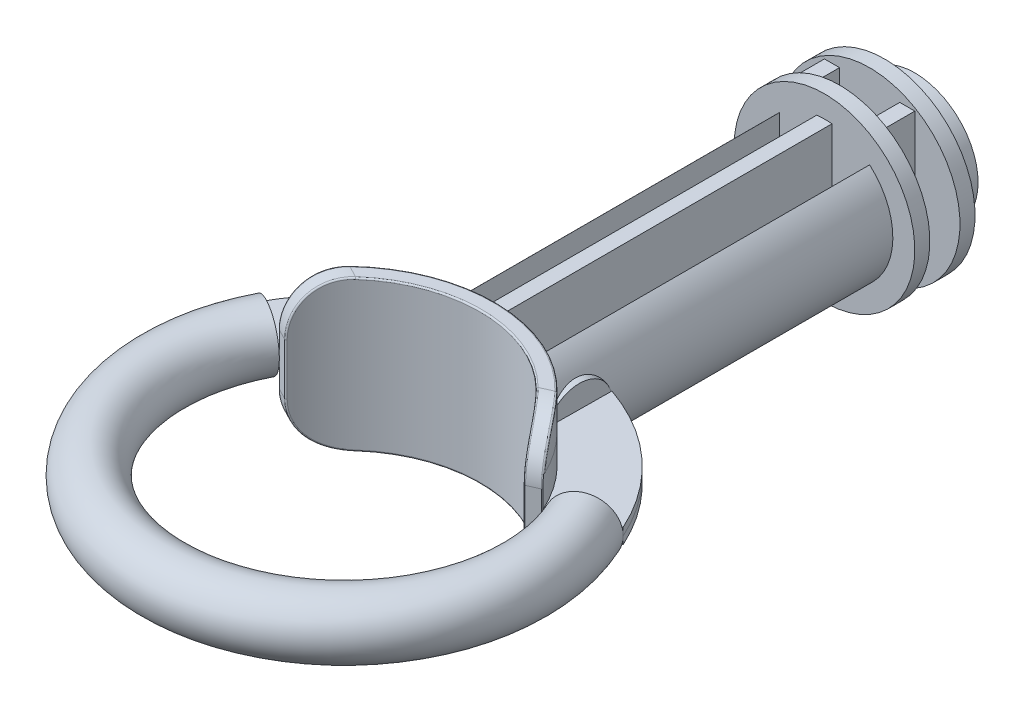
SolidWorks part; units mm, degrees
ref_plane "Front Plane" through (0, 0, 0) normal (0, 0, 1) x (1, 0, 0)
ref_plane "Top Plane" through (0, 0, 0) normal (0, 1, 0) x (1, 0, 0)
ref_plane "Right Plane" through (0, 0, 0) normal (1, 0, 0) x (0, 0, -1)
ref_axis "Axis1" through (0, 55, 0) along (0, -1, 0)
sketch "Sketch2" plane through (0, 0, 0) normal (0, 0, 1) x (1, 0, 0)
  circle A0 centre (12, 0) radius 2
  dimension "D1" = 12
revolve "Revolve1" add sketch "Sketch2" angle 360 about axis through (0, 55, 0) along (0, -1, 0)
ref_plane "Plane1" through (0, 0, -9.9) normal (0, 0, 1) x (1, 0, 0)
sketch "Sketch3" plane through (0, 0, -9.9) normal (0, 0, 1) x (1, 0, 0)
  circle A0 centre (0, 0) radius 4.5427
extrude "Boss-Extrude1" add sketch "Sketch3" against normal blind 22 and the other way blind 0.88
sketch "Sketch6" plane through (0, 0, 0) normal (0, 1, 0) x (1, 0, 0)
  line L0 (-8.901, 4.5576) -> (-8.0225, 4.1078)
  line L1 (9.1173, 4.1078) -> (8.2175, 3.7024)
  arc A0 (9.1173, 4.1078) -> (-8.901, 4.5576) centre (0, 0) ccw
  arc A1 (8.2175, 3.7024) -> (-8.0225, 4.1078) centre (0, 0) ccw
extrude "Boss-Extrude10" add sketch "Sketch6" along normal blind 5 and the other way blind 5 separate body
sketch "Sketch7" plane through (0, 0, -31.9) normal (0, 0, -1) x (-1, 0, 0)
  circle A0 centre (0, 0) radius 6
extrude "Boss-Extrude11" add sketch "Sketch7" along normal blind 1
fillet "Fillet1" radius 3.3 4 edges at (8.6674, 5, -3.9051) (-8.4617, 5, -4.3327) (-8.4617, -5, -4.3327) (8.6674, -5, -3.9051)
fillet "Fillet2" radius 0.1 16 edges at (8.5115, 4.3168, -5.2492) (9.1173, 0, -4.1078) (8.7971, -3.7597, -4.7551) (-8.239, -4.3168, -5.6674) (-8.901, 0, -4.5576) (-8.5489, 3.7597, -5.1881) (-7.345, 4.3264, -5.2236) (-8.0225, 0, -4.1078) (-7.668, -3.7593, -4.7367) (7.5965, -4.3264, -4.8506) (8.2175, 0, -3.7024) (7.8948, 3.7593, -4.3482) (0.2496, -5, -9.9969) (0.2249, -5, -9.0102) (0.2496, 5, -9.9969) (0.2249, 5, -9.0102)
sketch "Sketch9" plane through (0, 0, -32.9) normal (0, 0, -1) x (-1, 0, 0)
  line L0 (6.804, 5) -> (-7.1544, 5) construction
  line L1 (-1.9994, -5) -> (-3.0006, -5)
  line L2 (-1.9994, -5) -> (-1.9994, 5)
  line L3 (-1.9994, 5) -> (-3.0006, 5)
  line L4 (-3.0006, -5) -> (-3.0006, 5)
  line L5 (-1.9994, -5) -> (-3.0006, 5) construction
  line L6 (-1.9994, 5) -> (-3.0006, -5) construction
  point P0 (-2.5, 0)
  dimension "D1" = 2.5
extrude "Boss-Extrude12" add sketch "Sketch9" along normal blind 2
mirror "Mirror1" about plane through (0, 0, 0) normal (1, 0, 0) of "Boss-Extrude12"
sketch "Sketch10" plane through (0, 0, -32.9) normal (0, 0, -1) x (-1, 0, 0)
  line L0 (-1.9994, -5) -> (-1.9994, 5) construction
  line L1 (1.9994, -1.9998) -> (-1.9994, -1.9998)
  line L2 (1.9994, -1.9998) -> (1.9994, 1.9998)
  line L3 (1.9994, 1.9998) -> (-1.9994, 1.9998)
  line L4 (-1.9994, -1.9998) -> (-1.9994, 1.9998)
  line L5 (1.9994, -1.9998) -> (-1.9994, 1.9998) construction
  line L6 (1.9994, 1.9998) -> (-1.9994, -1.9998) construction
  point P0 (0, 0)
extrude "Boss-Extrude13" add sketch "Sketch10" along normal blind 2
sketch "Sketch11" plane through (0, 0, -34.9) normal (0, 0, -1) x (-1, 0, 0)
  circle A0 centre (0, 0) radius 6
extrude "Boss-Extrude14" add sketch "Sketch11" along normal blind 1
sketch "Sketch12" plane through (0, 0, -35.9) normal (0, 0, -1) x (-1, 0, 0)
  line L0 (-0.5, 0.5) -> (-0.5, 3)
  line L1 (0.5, -3) -> (-0.5, -3)
  line L2 (0.5, -3) -> (0.5, -0.5)
  line L3 (0.5, 3) -> (-0.5, 3)
  line L4 (-0.5, -3) -> (-0.5, -0.5)
  line L5 (0.5, -3) -> (-0.5, 3) construction
  line L6 (0.5, 3) -> (-0.5, -3) construction
  line L7 (3, -0.5) -> (0.5, -0.5)
  line L8 (3, -0.5) -> (3, 0.5)
  line L9 (3, 0.5) -> (0.5, 0.5)
  line L10 (-3, -0.5) -> (-3, 0.5)
  line L11 (-0.6451, 0.1075) -> (-3, 0.5) construction
  line L12 (3, 0.5) -> (-3, -0.5) construction
  line L13 (-0.5, 0.5) -> (-3, 0.5)
  line L14 (0.5, 0.5) -> (0.5, 3)
  line L16 (-0.5, -0.5) -> (-3, -0.5)
  point P0 (0, 0)
  point P6 (0, 0)
  dimension "D1" = 1
  dimension "D2" = 6
  dimension "D3" = 6
  dimension "D4" = 1
extrude "Boss-Extrude15" add sketch "Sketch12" along normal blind 1
sketch "Sketch13" plane through (0, 0, -36.9) normal (0, 0, -1) x (-1, 0, 0)
  circle A0 centre (0, 0) radius 4.2
extrude "Boss-Extrude16" add sketch "Sketch13" along normal blind 1
sketch "Sketch14" plane through (0, 0, -37.9) normal (0, 0, -1) x (-1, 0, 0)
  line L1 (0.5, -4.1701) -> (-0.5, -4.1701)
  line L2 (0.5, -4.1701) -> (0.5, -0.5)
  line L3 (0.5, 4.1701) -> (-0.5, 4.1701)
  line L4 (-0.5, -4.1701) -> (-0.5, -0.5)
  line L5 (0.5, -4.1701) -> (-0.5, 4.1701) construction
  line L6 (0.5, 4.1701) -> (-0.5, -4.1701) construction
  line L7 (4.1701, -0.5) -> (0.5, -0.5)
  line L8 (4.1701, -0.5) -> (4.1701, 0.5)
  line L9 (4.1701, 0.5) -> (0.5, 0.5)
  line L10 (-4.1701, -0.5) -> (-4.1701, 0.5)
  line L11 (4.1701, -0.5) -> (-4.1701, 0.5) construction
  line L12 (4.1701, 0.5) -> (-4.1701, -0.5) construction
  line L13 (-0.5, 0.5) -> (-4.1701, 0.5)
  line L14 (-0.5, -0.5) -> (-4.1701, -0.5)
  line L15 (-0.5, 0.5) -> (-0.5, 4.1701)
  line L17 (0.5, 0.5) -> (0.5, 4.1701)
  circle A0 centre (0, 0) radius 4.2 construction
  point P0 (0, 0)
  point P8 (0, 0)
  dimension "D1" = 1
  dimension "D2" = 1
extrude "Boss-Extrude17" add sketch "Sketch14" along normal blind 1
fillet "Fillet3" radius 7 4 edges at (0, -4.1701, -38.9) (4.1701, 0, -38.9) (0, 4.1701, -38.9) (-4.1701, 0, -38.9)
ref_plane "Plane2" through (0, 4.6, 0) normal (0, 1, 0) x (1, 0, 0)
sketch "Sketch15" plane through (0, 4.6, 0) normal (0, 1, 0) x (1, 0, 0)
  line L1 (-0.5082, 31.9) -> (-3, 31.9)
  line L3 (-0.5082, 9.9) -> (-3, 9.9)
  line L4 (-3, 31.9) -> (-3, 9.9)
  line L5 (-6.6, 9.9) -> (6.6, 9.9) construction
  line L7 (0.4944, 31.9) -> (3, 31.9)
  line L9 (0.4944, 9.9) -> (3, 9.9)
  line L10 (3, 31.9) -> (3, 9.9)
  line L11 (-0.5082, 31.9) -> (-0.5082, 9.9)
  line L13 (0.4944, 9.9) -> (0.4944, 31.9)
extrude "Cut-Extrude2" cut sketch "Sketch15" against normal blind 4
ref_plane "Plane3" through (0, -4.5, 0) normal (0, 1, 0) x (1, 0, 0)
sketch "Sketch16" plane through (0, -4.5, 0) normal (0, 1, 0) x (1, 0, 0)
  line L1 (0.4571, 31.8975) -> (2.9571, 31.8975)
  line L3 (0.4571, 9.8975) -> (2.9571, 9.8975)
  line L4 (2.9571, 31.8975) -> (2.9571, 9.8975)
  line L5 (-0.5988, 31.8975) -> (-3.0429, 31.8975)
  line L7 (-0.5988, 9.8975) -> (-3.0429, 9.8975)
  line L8 (-3.0429, 31.8975) -> (-3.0429, 9.8975)
  line L9 (0.4571, 31.8975) -> (0.4571, 9.8975)
  line L11 (-0.5988, 9.8975) -> (-0.5988, 31.8975)
  dimension "D3" = 22
extrude "Cut-Extrude3" cut sketch "Sketch16" along normal blind 4
sketch "Sketch17" plane through (0, 0, 0) normal (0, 1, 0) x (1, 0, 0)
  line L0 (-8.8607, 4.5688) -> (-12.4432, 6.4161)
  line L3 (-4.5707, 13.2329) -> (-4.5707, 8.8767)
  arc A0 (-4.5427, 13.2425) -> (4.5427, 13.2425) centre (0, 0) ccw construction
  arc A1 (-12.4432, 6.4161) -> (-4.5707, 13.2329) centre (0, 0) cw
  arc A2 (-8.8607, 4.5688) -> (-4.5707, 8.8767) centre (-0.2821, 0.3158) cw
extrude "Cut-Extrude4" cut sketch "Sketch17" against normal blind 2
extrude "Boss-Extrude20" add sketch "Sketch17<2>" against normal blind 0.5 separate body
sketch "Sketch17<2>" plane through (0, 0, 0) normal (0, 1, 0) x (1, 0, 0) same geometry as "Sketch17"
extrude "Cut-Extrude5" cut sketch "Sketch17<3>" along normal blind 2.5
sketch "Sketch17<3>" plane through (0, 0, 0) normal (0, 1, 0) x (1, 0, 0) same geometry as "Sketch17"
extrude "Boss-Extrude22" add sketch "Sketch17<4>" along normal blind 0.5 separate body
sketch "Sketch17<4>" plane through (0, 0, 0) normal (0, 1, 0) x (1, 0, 0) same geometry as "Sketch17"
sketch "Sketch18" plane through (0, 0, 0) normal (0, 1, 0) x (1, 0, 0)
  line L0 (9.0783, 4.1228) -> (12.7471, 5.7889)
  line L1 (4.5427, 13.2425) -> (4.5427, 31.9) construction
  line L2 (-4.5067, 9.02) -> (4.5067, 9.02) construction
  line L3 (4.5427, 13.2425) -> (4.5067, 9.02)
  arc A0 (9.0257, 4.0665) -> (9.0754, 4.1997) centre (8.9846, 4.1577) ccw construction
  arc A1 (-12.4432, 6.4161) -> (4.5427, 13.2425) centre (0, 0) ccw construction
  arc A2 (12.7471, 5.7889) -> (4.5427, 13.2425) centre (0, 0) ccw
  arc A3 (9.0783, 4.1228) -> (4.5067, 9.02) centre (-0.4732, -0.2113) ccw
extrude "Cut-Extrude6" cut sketch "Sketch18" against normal blind 2.5
extrude "Boss-Extrude23" add sketch "Sketch18<2>" against normal blind 0.5 separate body
sketch "Sketch18<2>" plane through (0, 0, 0) normal (0, 1, 0) x (1, 0, 0) same geometry as "Sketch18"
extrude "Cut-Extrude8" cut sketch "Sketch18<4>" along normal blind 2.5
sketch "Sketch18<4>" plane through (0, 0, 0) normal (0, 1, 0) x (1, 0, 0) same geometry as "Sketch18"
extrude "Boss-Extrude24" add sketch "Sketch18<5>" along normal blind 0.5 separate body
sketch "Sketch18<5>" plane through (0, 0, 0) normal (0, 1, 0) x (1, 0, 0) same geometry as "Sketch18"
